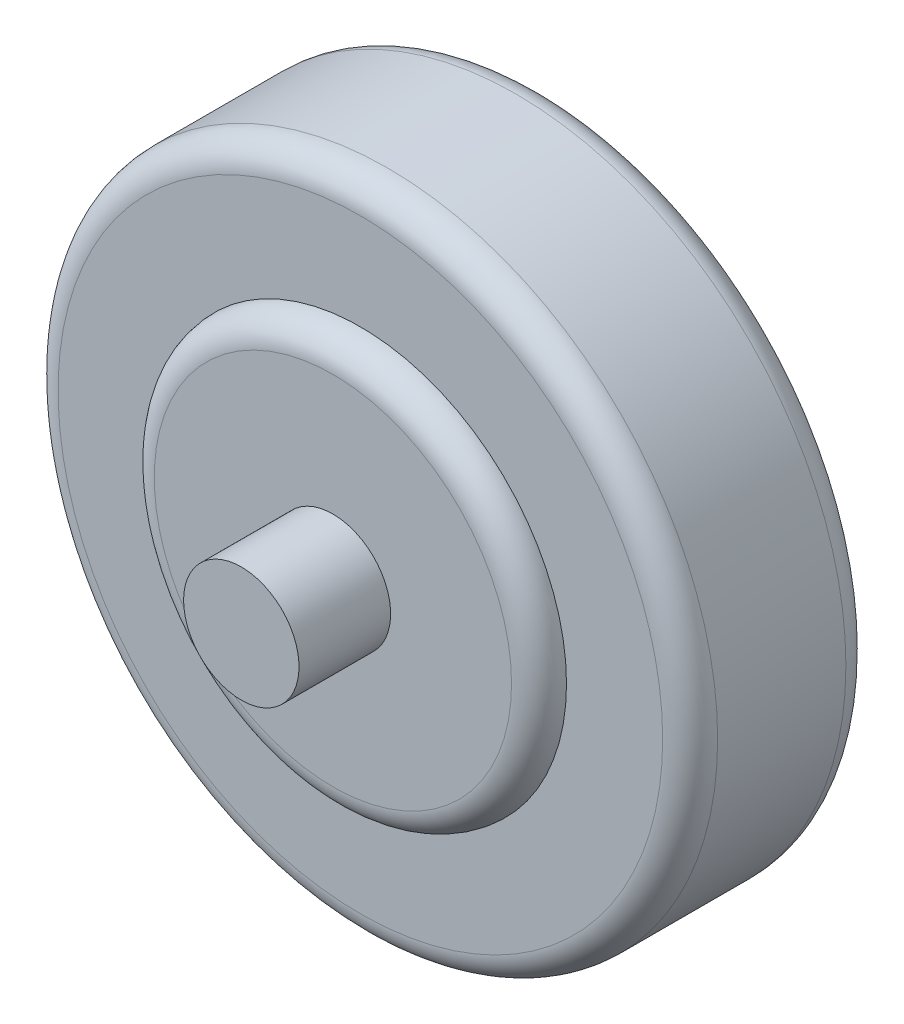
SolidWorks part; units mm, degrees
ref_plane "Front Plane" through (0, 0, 0) normal (0, 0, 1) x (1, 0, 0)
ref_plane "Top Plane" through (0, 0, 0) normal (0, 1, 0) x (1, 0, 0)
ref_plane "Right Plane" through (0, 0, 0) normal (1, 0, 0) x (0, 0, -1)
sketch "Sketch1" plane through (0, 0, 0) normal (0, 0, 1) x (1, 0, 0)
  circle A0 centre (0, 0) radius 360
  dimension "D1" = 720
extrude "Boss-Extrude1" add sketch "Sketch1" along normal blind 200
sketch "Sketch2" plane through (0, 0, 200) normal (0, 0, 1) x (1, 0, 0)
  circle A0 centre (0, 0) radius 225
  dimension "D1" = 450
extrude "Boss-Extrude2" add sketch "Sketch2" along normal blind 30
sketch "Sketch3" plane through (0, 0, 230) normal (0, 0, 1) x (1, 0, 0)
  circle A0 centre (0, 0) radius 63
  dimension "D1" = 126
extrude "Boss-Extrude3" add sketch "Sketch3" along normal blind 100
fillet "Fillet1" radius 30 3 edges at (225, 0, 230) (360, 0, 200) (360, 0, 0)
sketch "Sketch4" plane through (0, 0, 0) normal (0, 0, -1) x (-1, 0, 0)
  circle A0 centre (0, 0) radius 201.8869
extrude "Cut-Extrude1" cut sketch "Sketch4" against normal blind 40
fillet "Fillet2" radius 30 1 edges at (-201.8869, 0, 0)
fillet "Fillet3" radius 30 1 edges at (-201.8869, 0, 40)
sketch "Sketch5" plane through (0, 0, 40) normal (0, 0, -1) x (-1, 0, 0)
  circle A0 centre (0, 0) radius 89.3112
extrude "Boss-Extrude4" add sketch "Sketch5" along normal blind 30
fillet "Fillet4" radius 30 1 edges at (-89.3112, 0, 40)
fillet "Fillet5" radius 30 1 edges at (-89.3112, 0, 10)
